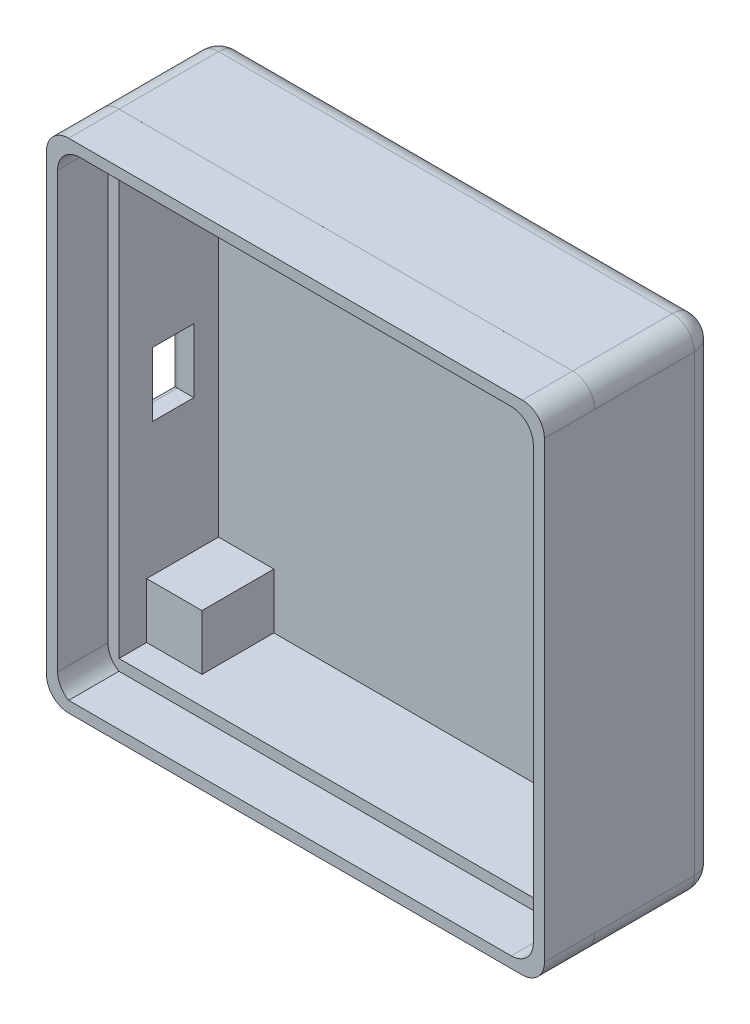
SolidWorks part; units mm, degrees
ref_plane "Piano frontale" through (0, 0, 0) normal (0, 0, 1) x (1, 0, 0)
ref_plane "Piano superiore" through (0, 0, 0) normal (0, 1, 0) x (1, 0, 0)
ref_plane "Piano destro" through (0, 0, 0) normal (1, 0, 0) x (0, 0, -1)
sketch "Schizzo2" plane through (0, 0, 0) normal (0, 0, 1) x (1, 0, 0)
  line L1 (0, 0) -> (45, 0)
  line L2 (0, 0) -> (0, 45)
  line L3 (0, 45) -> (45, 45)
  line L4 (45, 0) -> (45, 45)
  dimension "D1" = 45
  dimension "D2" = 45
extrude "Estrusione-Estrusione2" add sketch "Schizzo2" along normal blind 11
shell "Svuota1" thickness 2 removed face at (22.5, 22.5, 11)
fillet "Raccordo1" radius 2 4 edges at (45, 45, 5.5) (45, 0, 5.5) (0, 0, 5.5) (0, 45, 5.5)
fillet "Raccordo2" radius 2 8 edges at (44.4142, 0.5858, 0) (22.5, 0, 0) (0.5858, 0.5858, 0) (0, 22.5, 0) (0.5858, 44.4142, 0) (22.5, 45, 0) (44.4142, 44.4142, 0) (45, 22.5, 0)
sketch "Schizzo3" plane through (0, 0, 2) normal (0, 0, 1) x (1, 0, 0)
  line L0 (43, 43) -> (2, 43) construction
  line L1 (2, 43) -> (7, 43)
  line L2 (2, 43) -> (2, 38)
  line L3 (2, 38) -> (7, 38)
  line L4 (7, 43) -> (7, 38)
  line L5 (43, 43) -> (2, 43) construction
  dimension "D1" = 5
  dimension "D2" = 5
extrude "Estrusione-Estrusione3" add sketch "Schizzo3" along normal blind 6.5
sketch "Schizzo4" plane through (0, 0, 2) normal (0, 0, 1) x (1, 0, 0)
  line L1 (43, 2) -> (38, 2)
  line L2 (43, 2) -> (43, 7)
  line L3 (43, 7) -> (38, 7)
  line L4 (38, 2) -> (38, 7)
  dimension "D1" = 5
  dimension "D2" = 5
extrude "Estrusione-Estrusione4" add sketch "Schizzo4" along normal blind 6.5
fillet "Raccordo3" radius 4 2 edges at (38, 7, 5.25) (7, 38, 5.25)
sketch "Schizzo5" plane through (0, 0, 2) normal (0, 0, 1) x (1, 0, 0)
  line L0 (43, 2) -> (43, 43) construction
  line L1 (43, 43) -> (38, 43)
  line L2 (43, 43) -> (43, 38)
  line L3 (43, 38) -> (38, 38)
  line L4 (38, 43) -> (38, 38)
  line L5 (43, 43) -> (7, 43) construction
  line L7 (2, 2) -> (7, 2)
  line L8 (2, 2) -> (2, 7)
  line L9 (2, 7) -> (7, 7)
  line L10 (7, 2) -> (7, 7)
  dimension "D1" = 5
  dimension "D2" = 5
  dimension "D3" = 5
  dimension "D4" = 5
extrude "Estrusione-Estrusione5" add sketch "Schizzo5" along normal blind 6.5 contours L2 L1 L4 L3 | L8 L7 L10 L9
sketch "Schizzo7" plane through (0, 0, 0) normal (-1, 0, 0) x (0, 0, 1)
  line L1 (4.2347, 24.8244) -> (7.9559, 24.8244)
  line L2 (4.2347, 24.8244) -> (4.2347, 19.0329)
  line L3 (4.2347, 19.0329) -> (7.9559, 19.0329)
  line L4 (7.9559, 24.8244) -> (7.9559, 19.0329)
extrude "Taglio-Estrusione1" cut sketch "Schizzo7" against normal blind 3
sketch "Schizzo9" plane through (0, 0, 0) normal (-1, 0, 0) x (0, 0, 1)
  circle A0 centre (3.8708, 40.998) radius 1
  dimension "D1" = 2
extrude "Taglio-Estrusione2" cut sketch "Schizzo9" against normal blind 2
sketch "Schizzo12" plane through (0, 0, 11) normal (0, 0, 1) x (1, 0, 0)
  line L1 (0, 44.9999) -> (45, 44.9999)
  line L2 (0, 44.9999) -> (0, 43.9999)
  line L3 (0, 43.9999) -> (45, 43.9999)
  line L4 (45, 44.9999) -> (45, 43.9999)
  dimension "D1" = 45
  dimension "D2" = 1
extrude "Estrusione-Estrusione7" add sketch "Schizzo12" along normal blind 4.55
sketch "Schizzo13" plane through (0, 0, 11) normal (0, 0, 1) x (1, 0, 0)
  line L1 (45, 43.9999) -> (44, 43.9999)
  line L2 (45, 43.9999) -> (45, -0.0001)
  line L3 (45, -0.0001) -> (44, -0.0001)
  line L4 (44, 43.9999) -> (44, -0.0001)
  dimension "D1" = 44
  dimension "D2" = 1
extrude "Estrusione-Estrusione10" add sketch "Schizzo13" along normal blind 4.55
sketch "Schizzo15" plane through (0, 0, 11) normal (0, 0, 1) x (1, 0, 0)
  line L1 (44, -0.0001) -> (2, -0.0001)
  line L2 (44, -0.0001) -> (44, 0.9999)
  line L3 (44, 0.9999) -> (2, 0.9999)
  line L4 (2, -0.0001) -> (2, 0.9999)
  dimension "D1" = 1
  dimension "D2" = 42
extrude "Estrusione-Estrusione11" add sketch "Schizzo15" along normal blind 4.55
fillet "Raccordo4" radius 2 1 edges at (45, -0.0001, 13.275)
fillet "Raccordo5" radius 2 1 edges at (45, 44.9999, 13.275)
sketch "Schizzo17" plane through (0, 0, 11) normal (0, 0, 1) x (1, 0, 0)
  line L1 (0, 43.9999) -> (1, 43.9999)
  line L2 (0, 43.9999) -> (0, -0.0001)
  line L3 (0, -0.0001) -> (1, -0.0001)
  line L4 (1, 43.9999) -> (1, -0.0001)
  dimension "D1" = 1
  dimension "D2" = 44
extrude "Estrusione-Estrusione13" add sketch "Schizzo17" along normal blind 4.55
fillet "Raccordo6" radius 2 1 edges at (0, 44.9999, 13.275)
fillet "Raccordo7" radius 2 1 edges at (44, 0.9999, 13.275)
fillet "Raccordo8" radius 2 1 edges at (44, 43.9999, 13.275)
fillet "Raccordo9" radius 2 1 edges at (1, 43.9999, 13.275)
sketch "Schizzo18" plane through (0, 0, 11) normal (0, 0, 1) x (1, 0, 0)
  line L0 (1, -0.0001) -> (1, 41.9999) construction
  line L1 (2, -0.0001) -> (1, -0.0001)
  line L2 (2, -0.0001) -> (2, 0.9995)
  line L3 (2, 0.9995) -> (1, 0.9995)
  line L4 (1, -0.0001) -> (1, 0.9995)
extrude "Estrusione-Estrusione14" add sketch "Schizzo18" along normal blind 4.55
fillet "Raccordo10" radius 2 1 edges at (0, -0.0001, 13.275)
fillet "Raccordo11" radius 2 1 edges at (1, 0.9995, 13.275)
fillet "Raccordo12" radius 0.5 4 edges at (0, 19.0329, 6.0953) (0, 21.9286, 7.9559) (0, 21.9286, 4.2347) (0, 24.8244, 6.0953)
